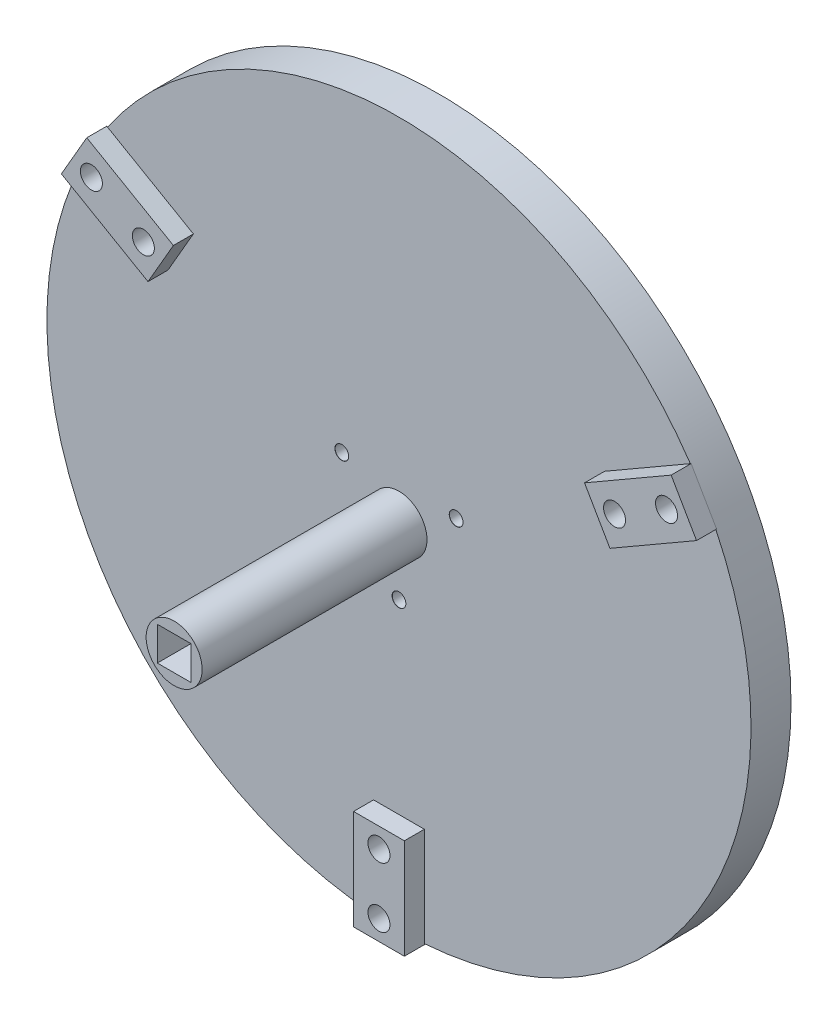
SolidWorks part; units mm, degrees
ref_plane "Front Plane" through (0, 0, 0) normal (0, 0, 1) x (1, 0, 0)
ref_plane "Top Plane" through (0, 0, 0) normal (0, 1, 0) x (1, 0, 0)
ref_plane "Right Plane" through (0, 0, 0) normal (1, 0, 0) x (0, 0, -1)
sketch "Sketch1" plane through (0, 0, 0) normal (0, 0, 1) x (1, 0, 0)
  circle A0 centre (0, 0) radius 88
  dimension "D1" = 176
extrude "Boss-Extrude1" add sketch "Sketch1" along normal blind 10
sketch "Sketch14" plane through (0, 0, 10) normal (0, 0, 1) x (1, 0, 0)
  line L0 (0, 0) -> (0, -88) construction
  line L2 (-6.35, -88) -> (6.35, -88)
  line L7 (-6.35, -88) -> (-6.35, -63)
  line L8 (-6.35, -63) -> (6.35, -63)
  line L9 (6.35, -88) -> (6.35, -63)
  line L10 (-6.35, -8) -> (6.35, -8) construction
  line L11 (-6.35, -8) -> (-6.35, -33) construction
  line L12 (-6.35, -33) -> (6.35, -33) construction
  line L13 (6.35, -8) -> (6.35, -33) construction
  circle A1 centre (0, 0) radius 88 construction
  point P12 (0, -88)
  dimension "D1" = 12.7
  dimension "D2" = 25
  dimension "D3" = 80
extrude "Boss-Extrude4" add sketch "Sketch14" along normal blind 5
sketch "Sketch19" plane through (0, 0, 0) normal (0, 0, -1) x (-1, 0, 0)
  line L2 (0, -68) -> (0, -83) construction
  line L4 (-6.35, -88) -> (-6.35, -63) construction
  point P0 (0, -83)
  point P2 (0, -68)
  point P28 (-6.35, -75.5)
  point P29 (0, -75.5)
  dimension "D1" = 15
hole_wizard "M5 Clearance Hole1" positions "Sketch19" profile "Sketch18" hole size "M5" standard "ANSI Metric" end condition through all
sketch "Sketch18" plane through (0, -83, 0) normal (1, 0, 0) x (0, 1, 0)
  line L0 (0, 0) -> (0, 15)
  line L1 (0, 15) -> (2.75, 15)
  line L2 (2.75, 15) -> (2.75, 0)
  line L5 (2.75, 0) -> (0, 0)
  line L11 (0, -6.35) -> (0, 107.95) construction
  dimension "Thru Hole Dia." = 5.5
  dimension "Thru Hole Depth" = 15
ref_axis "Axis2" through (0, 0, 38.9853) along (0, 0, -1)
pattern_circular "CirPattern2" count 3 every 120 about axis through (0, 0, 38.9853) along (0, 0, -1) of "Boss-Extrude4", "M5 Clearance Hole1"
sketch "Sketch2" plane through (0, 0, 10) normal (0, 0, 1) x (1, 0, 0)
  line L0 (0, 0) -> (0, -16.5) construction
  line L1 (-14.2894, 8.25) -> (0, 0) construction
  line L2 (0, 0) -> (14.2894, 8.25) construction
  circle A0 centre (0, 0) radius 16.5 construction
  point P7 (-14.2894, 8.25)
  point P8 (14.2894, 8.25)
  point P9 (0, -16.5)
  dimension "D1" = 33
  dimension "D2" = 120
  dimension "D3" = 120
sketch "Sketch5" plane through (0, 0, 10) normal (0, 0, 1) x (1, 0, 0)
  point P0 (-14.2894, 8.25)
  point P3 (14.2894, 8.25)
  point P6 (0, -16.5)
hole_wizard "M3 Clearance Hole1" positions "Sketch5" profile "Sketch4" hole size "M3" standard "ANSI Metric" end condition up to next
sketch "Sketch4" plane through (-14.2894, 8.25, 10) normal (1, 0, 0) x (0, -1, 0)
  line L0 (0, 0) -> (0, 10)
  line L1 (0, 10) -> (1.7, 10)
  line L2 (1.7, 10) -> (1.7, 0.025)
  line L3 (1.7, 0.025) -> (1.725, 0)
  line L5 (1.725, 0) -> (0, 0)
  line L6 (-1.7, 0.025) -> (-1.725, 0) construction
  line L11 (0, -6.35) -> (0, 107.95) construction
  dimension "Thru Hole Dia." = 3.4
  dimension "Thru Hole Depth" = 10
  dimension "Near C'Sink Dia." = 3.45
  dimension "Near C'Sink Angle" = 90
sketch "Sketch6" plane through (0, 0, 10) normal (0, 0, 1) x (1, 0, 0)
  circle A0 centre (0, 0) radius 7
  dimension "D1" = 14
extrude "Boss-Extrude2" add sketch "Sketch6" along normal blind 56.2
sketch "Sketch20" plane through (0, 0, 66.2) normal (0, 0, 1) x (1, 0, 0)
  line L1 (-4.2, 4.2) -> (4.2, 4.2)
  line L2 (-4.2, 4.2) -> (-4.2, -4.2)
  line L3 (-4.2, -4.2) -> (4.2, -4.2)
  line L4 (4.2, 4.2) -> (4.2, -4.2)
  line L5 (-4.2, 4.2) -> (4.2, -4.2) construction
  line L6 (-4.2, -4.2) -> (4.2, 4.2) construction
  point P0 (0, 0)
  dimension "D1" = 8.4
extrude "Cut-Extrude1" cut sketch "Sketch20" against normal blind 20
